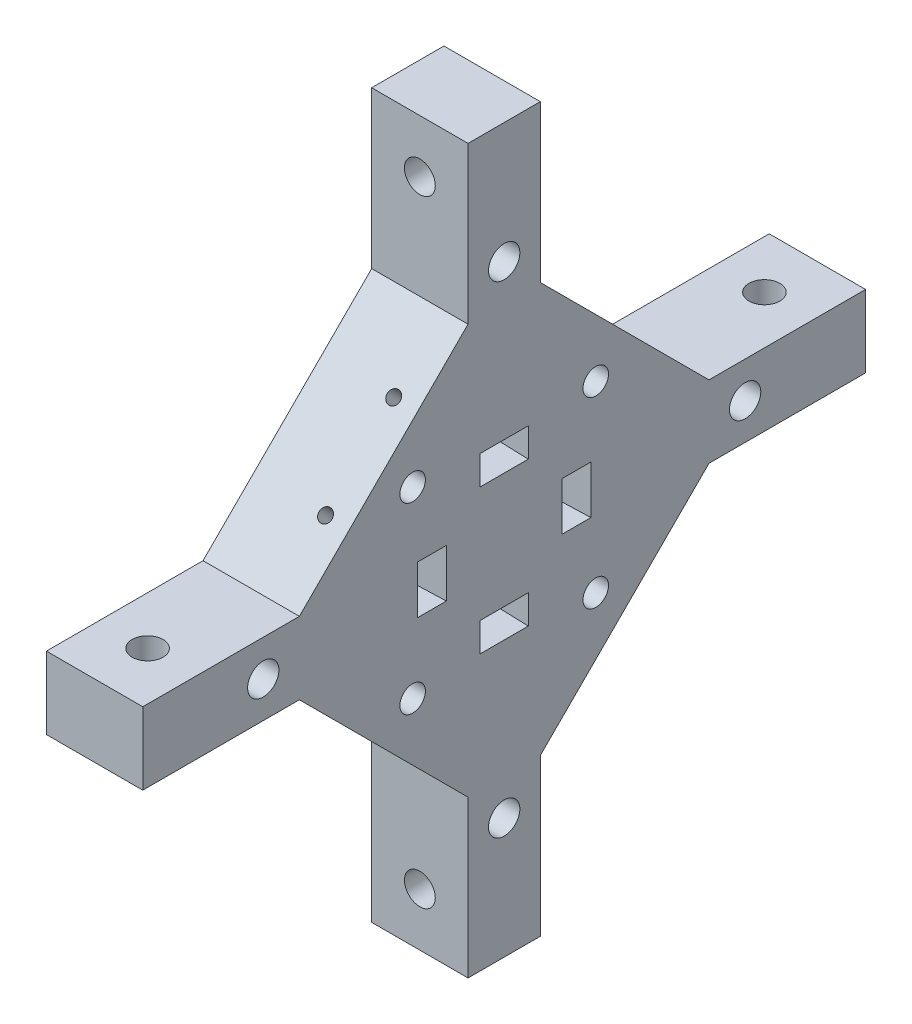
SolidWorks part; units mm, degrees
ref_plane "Front Plane" through (0, 0, 0) normal (0, 0, 1) x (1, 0, 0)
ref_plane "Top Plane" through (0, 0, 0) normal (0, 1, 0) x (1, 0, 0)
ref_plane "Right Plane" through (0, 0, 0) normal (1, 0, 0) x (0, 0, -1)
sketch "Sketch1" plane through (0, 0, 0) normal (1, 0, 0) x (0, 0, -1)
  line L1 (-25, 25) -> (25, 25)
  line L2 (-25, 25) -> (-25, -25)
  line L3 (-25, -25) -> (25, -25)
  line L4 (25, 25) -> (25, -25)
  line L5 (-25, 25) -> (25, -25) construction
  line L6 (-25, -25) -> (25, 25) construction
  circle A0 centre (-19, 19) radius 1.7
  circle A1 centre (19, 19) radius 1.7
  circle A2 centre (19, -19) radius 1.7
  circle A3 centre (-19, -19) radius 1.7
  point P0 (0, 0)
  point P17 (0, 0)
  dimension "D3" = 6
  dimension "D4" = 3.4
  dimension "D1" = 50
  dimension "D2" = 50
extrude "Boss-Extrude1" add sketch "Sketch1" along normal blind 20
sketch "Sketch2" plane through (20, 0, 0) normal (1, 0, 0) x (0, 0, -1)
  circle A0 centre (-19, 19) radius 2.65
  circle A1 centre (19, 19) radius 2.65
  circle A2 centre (19, -19) radius 2.65
  circle A3 centre (-19, -19) radius 2.65
  point P12 (0, 0)
  circle M3 centre (19, -19) radius 1.7
  circle M4 centre (-19, 19) radius 1.7
  circle M9 centre (19, 19) radius 1.7
  circle M10 centre (-19, -19) radius 1.7
  dimension "D1" = 5.3
  dimension "D2" = 4
extrude "Cut-Extrude1" cut sketch "Sketch2" against normal blind 12.5 contours A0 M4 | A1 M9 | A2 M3 | A3 M10 region at (20, 19, 21.575) region at (20, 19, -16.425) region at (20, -19, -16.425) region at (20, -19, 21.575)
sketch "Sketch3" plane through (0, 0, 0) normal (0, 1, 0) x (1, 0, 0)
  line L2 (0, 0) -> (0, 15.125)
  line L3 (0, 25) -> (0, -25) construction
  line L5 (15.125, 0) -> (0, 0)
  line L6 (-993.7626, 0) -> (49006.2374, 0) construction
  arc A1 (0, 15.125) -> (15.125, 0) centre (0, 0) cw
  dimension "D1" = 15.125
revolve "Cut-Revolve1" cut sketch "Sketch3" angle 360 about L6
sketch "Sketch4" plane through (20, 0, 0) normal (1, 0, 0) x (0, 0, -1)
  line L0 (25, 25) -> (42.5, 7.5)
  line L1 (42.5, 7.5) -> (75, 7.5)
  line L2 (75, 7.5) -> (75, -7.5)
  line L3 (75, -7.5) -> (42.5, -7.5)
  line L4 (42.5, -7.5) -> (25, -25)
  line L5 (25, -25) -> (25, 25) construction
  line L6 (25, 25) -> (-25, 25) construction
  line L7 (25, 25) -> (25, -25)
  line L8 (25, -25) -> (7.5, -42.5)
  line L9 (7.5, -42.5) -> (7.5, -75)
  line L10 (7.5, -75) -> (-7.5, -75)
  line L11 (-7.5, -75) -> (-7.5, -42.5)
  line L12 (-7.5, -42.5) -> (-25, -25)
  line L13 (25, -25) -> (-25, -25)
  line L14 (-25, -25) -> (-42.5, -7.5)
  line L15 (-42.5, -7.5) -> (-75, -7.5)
  line L16 (-75, -7.5) -> (-75, 7.5)
  line L17 (-75, 7.5) -> (-42.5, 7.5)
  line L18 (-42.5, 7.5) -> (-25, 25)
  line L19 (-25, -25) -> (-25, 25)
  line L20 (-25, 25) -> (-7.5, 42.5)
  line L21 (-7.5, 42.5) -> (-7.5, 75)
  line L22 (-7.5, 75) -> (7.5, 75)
  line L23 (7.5, 75) -> (7.5, 42.5)
  line L24 (7.5, 42.5) -> (25, 25)
  line L25 (-25, 25) -> (25, 25)
  point P32 (0, 0)
  dimension "D1" = 45
  dimension "D2" = 45
  dimension "D3" = 50
  dimension "D4" = 17.5
  dimension "D5" = 4
extrude "Boss-Extrude3" add sketch "Sketch4" along direction (1, 0, 0) on the side against the normal up to surface (20 mm away) contours L18 L17 L16 L15 L14 | L24 L23 L22 L21 L20 L25 | L4 L3 L2 L1 L0 L24 | L12 L11 L10 L9 L8 region at (20, 0, -44.4428) region at (20, 44.4428, 0) region at (20, -44.4428, 0) region at (20, 0, 44.4428) up to face at (0, 0, 15.125)
sketch "Sketch5" plane through (20, 0, 0) normal (1, 0, 0) x (0, 0, -1)
  line L0 (17, 5) -> (17, -5)
  line L1 (-5, 17) -> (5, 17)
  line L2 (-5, 17) -> (-5, 13)
  line L3 (-5, 13) -> (5, 13)
  line L4 (5, 17) -> (5, 13)
  line L5 (-5, 17) -> (5, 13) construction
  line L6 (-5, 13) -> (5, 17) construction
  line L7 (17, 5) -> (13, 5)
  line L8 (13, 5) -> (13, -5)
  line L9 (17, -5) -> (13, -5)
  line L10 (17, 5) -> (13, -5) construction
  line L11 (13, 5) -> (17, -5) construction
  line L12 (5, -17) -> (-5, -17)
  line L13 (5, -17) -> (5, -13)
  line L14 (5, -13) -> (-5, -13)
  line L15 (-5, -17) -> (-5, -13)
  line L16 (5, -17) -> (-5, -13) construction
  line L17 (5, -13) -> (-5, -17) construction
  line L18 (-17, -5) -> (-17, 5)
  line L19 (-17, -5) -> (-13, -5)
  line L20 (-13, -5) -> (-13, 5)
  line L21 (-17, 5) -> (-13, 5)
  line L22 (-17, -5) -> (-13, 5) construction
  line L23 (-13, -5) -> (-17, 5) construction
  point P0 (0, 15)
  point P7 (15, 0)
  point P14 (0, -15)
  point P19 (-15, 0)
  point P24 (0, 0)
  dimension "D1" = 4
  dimension "D2" = 10
  dimension "D3" = 15
  dimension "D4" = 4
extrude "Cut-Extrude2" cut sketch "Sketch5" against normal blind 8
chamfer "Chamfer1" distance 1 angle 88 8 edges at (20, 0, 13) (20, 0, 17) (20, -13, 0) (20, -17, 0) (20, 13, 0) (20, 17, 0) (20, 0, -13) (20, 0, -17) first distance on face at (20, 15, 0)
sketch "Sketch7" plane through (20, 0, 0) normal (1, 0, 0) x (0, 0, -1)
  line L0 (75, 7.5) -> (75, -7.5) construction
  circle A0 centre (50, 0) radius 3.25
  circle A1 centre (0, -50) radius 3.25
  circle A2 centre (-50, 0) radius 3.25
  circle A3 centre (0, 50) radius 3.25
  point P13 (0, 0)
  dimension "D1" = 6.5
  dimension "D3" = 4
  dimension "D2" = 25
extrude "Cut-Extrude4" cut sketch "Sketch7" against normal through all both and the other way through all
sketch "Sketch8" plane through (0, -7.5, 0) normal (0, -1, 0) x (1, 0, 0)
  line L1 (0, -42.5) -> (0, -75) construction
  line L2 (0, -75) -> (20, -75) construction
  circle A0 centre (10, -64) radius 3.2
  dimension "D1" = 6.4
  dimension "D2" = 10
  dimension "D3" = 11
extrude "Cut-Extrude5" cut sketch "Sketch8" against normal through all both and the other way through all
pattern_circular "CirPattern1" count 4 over 360 about axis through (20, 0, 0) along (1, 0, 0) of "Cut-Extrude5"
sketch "Sketch9" plane through (0, -25, -25) normal (0, -0.7071, -0.7071) x (1, 0, 0)
  line L1 (0, 24.7487) -> (0, -24.7487) construction
  circle A0 centre (15, 10) radius 1.35
  circle A1 centre (15, -10) radius 1.35
  dimension "D1" = 2.7
  dimension "D2" = 15
  dimension "D3" = 10
  dimension "D4" = 2.7
  dimension "D5" = 10
extrude "Cut-Extrude6" cut sketch "Sketch9" against normal blind 15
pattern_circular "CirPattern2" count 4 over 360 about axis through (20, 0, 0) along (1, 0, 0) of "Cut-Extrude6"
